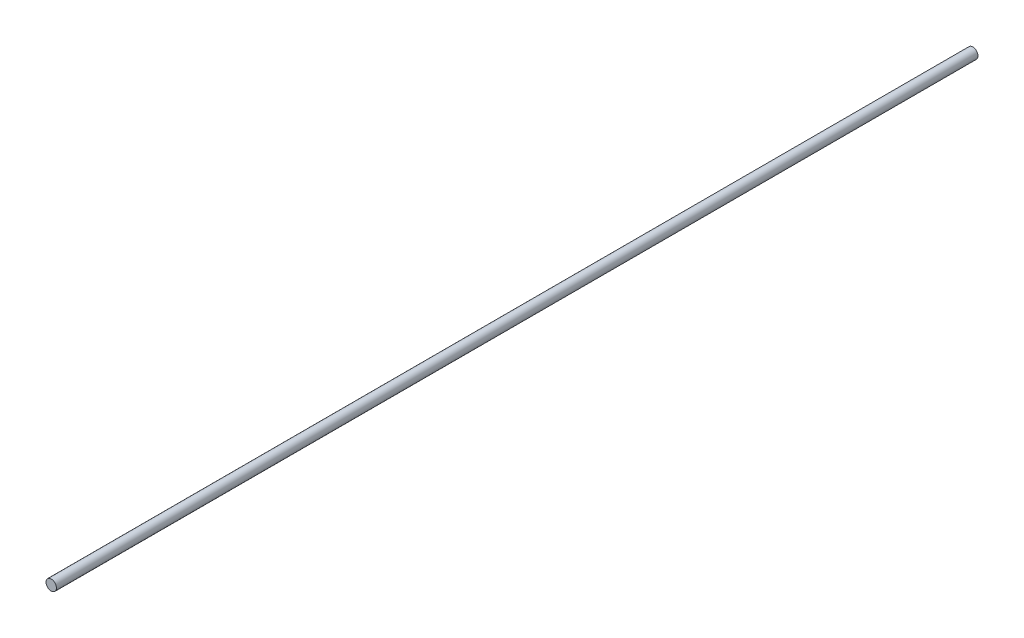
SolidWorks part; units mm, degrees
ref_plane "Front Plane" through (0, 0, 0) normal (0, 0, 1) x (1, 0, 0)
ref_plane "Top Plane" through (0, 0, 0) normal (0, 1, 0) x (1, 0, 0)
ref_plane "Right Plane" through (0, 0, 0) normal (1, 0, 0) x (0, 0, -1)
sketch "Sketch1" plane through (0, 0, 0) normal (0, 0, 1) x (1, 0, 0)
  circle A0 centre (0, 0) radius 4
  dimension "D1" = 8
extrude "Boss-Extrude1" add sketch "Sketch1" along normal blind 706
sketch "Sketch2" plane through (0, 0, 0) normal (1, 0, 0) x (0, 0, -1)
  line L0 (-706, 2.5) -> (-373.7449, 4.5)
  line L1 (-706, 4) -> (-706, -4) construction
  line L2 (-373.7449, 4.5) -> (-375.2449, 4.5)
  line L3 (-375.2449, 4.5) -> (-706, 2.5)
  line L4 (-706, 2.5) -> (-374.4949, 4.5) construction
  dimension "D1" = 1.5
  dimension "D2" = 2
  dimension "D3" = 0.5
sketch "Sketch3" plane through (0, 0, 706) normal (0, 0, 1) x (1, 0, 0)
  circle A0 centre (0, 0) radius 4
curve "Helix/Spiral1" pitch 8 height 380 radius 4 centre (0, 0, 706) axis (0, 0, -1) start towards (-0.682, 0.7314, 0)
sweep "Cut-Sweep1" cut profiles "Sketch2" path "Helix/Spiral1" rebuild error yes
